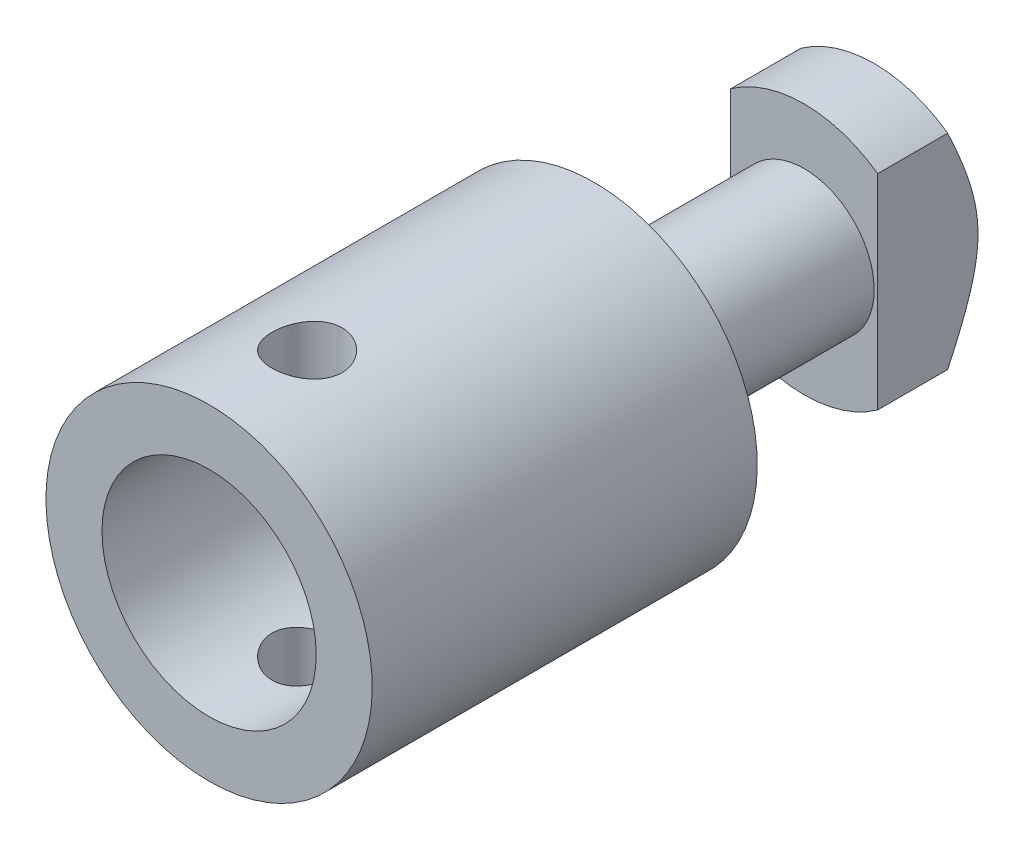
SolidWorks part; units mm, degrees
material "AISI Type 316L stainless steel"
ref_plane "Front" through (0, 0, 0) normal (0, 0, 1) x (1, 0, 0)
ref_plane "Top" through (0, 0, 0) normal (0, 1, 0) x (1, 0, 0)
ref_plane "Right" through (0, 0, 0) normal (1, 0, 0) x (0, 0, -1)
ref_axis "X" through (-80.9, 0, 0) along (1, 0, 0)
ref_axis "Y" through (0, -50, 0) along (0, 1, 0)
ref_axis "Z" through (0, 0, -80.9) along (0, 0, 1)
sketch "Sketch1" plane through (0, 0, 0) normal (1, 0, 0) x (0, 0, -1)
  line L0 (-2.9655, 0) -> (2.9655, 0) construction
  line L1 (0, 2.33) -> (5.5, 2.33)
  line L2 (5.5, 2.33) -> (5.5, 1)
  line L3 (5.5, 1) -> (8.5, 1)
  line L4 (8.5, 1) -> (8.5, 1.8)
  line L5 (8.5, 1.8) -> (9.5, 1.8)
  line L8 (9.5, 1.8) -> (10.5392, 0)
  line L10 (0, 1.53) -> (0, 2.33)
  line L11 (0, 1.53) -> (4, 1.53)
  line L12 (4, 1.53) -> (4, 0)
  line L13 (4, 0) -> (10.5392, 0)
  point P10 (10.1139, 2.226)
  point P13 (10.0613, 0)
  point P15 (11.1042, 0.8542)
  point P17 (15.3622, 0)
  point P18 (12.0998, 0)
  dimension "D1" = 3.06
  dimension "D2" = 0.8
  dimension "D3" = 4
  dimension "D4" = 1.5
  dimension "D5" = 30
  dimension "D6" = 2
  dimension "D7" = 1
  dimension "D8" = 0.8
  dimension "D9" = 3
revolve "Revolve1" add sketch "Sketch1" angle 360 about L0
sketch "Sketch2" plane through (0, 0, 0) normal (0, 0, 1) x (1, 0, 0)
  line L0 (1.05, 5) -> (1.05, -5)
  line L1 (1.05, -5) -> (6.05, -5)
  line L2 (6.05, -5) -> (6.05, 5)
  line L3 (6.05, 5) -> (1.05, 5)
  line L4 (-6.05, 5) -> (-6.05, -5)
  line L5 (-6.05, -5) -> (-1.05, -5)
  line L6 (-1.05, -5) -> (-1.05, 5)
  line L7 (-1.05, 5) -> (-6.05, 5)
  line L8 (0, 0) -> (1.05, 0) construction
  line L9 (0, 0) -> (-1.05, 0) construction
  dimension "D1" = 2.1
  dimension "D2" = 10
  dimension "D3" = 5
extrude "Cut-Extrude1" cut sketch "Sketch2" against normal through all from surface starting at face at (0, -1, -8.5)
sketch "Sketch3" plane through (0, 0, 0) normal (0, 1, 0) x (1, 0, 0)
  line L0 (0, 1.4) -> (0, 0) construction
  circle A0 centre (0, 1.4) radius 0.5
  dimension "D1" = 1
  dimension "D2" = 1.4
extrude "Cut-Extrude2" cut sketch "Sketch3" against normal through all both and the other way through all
